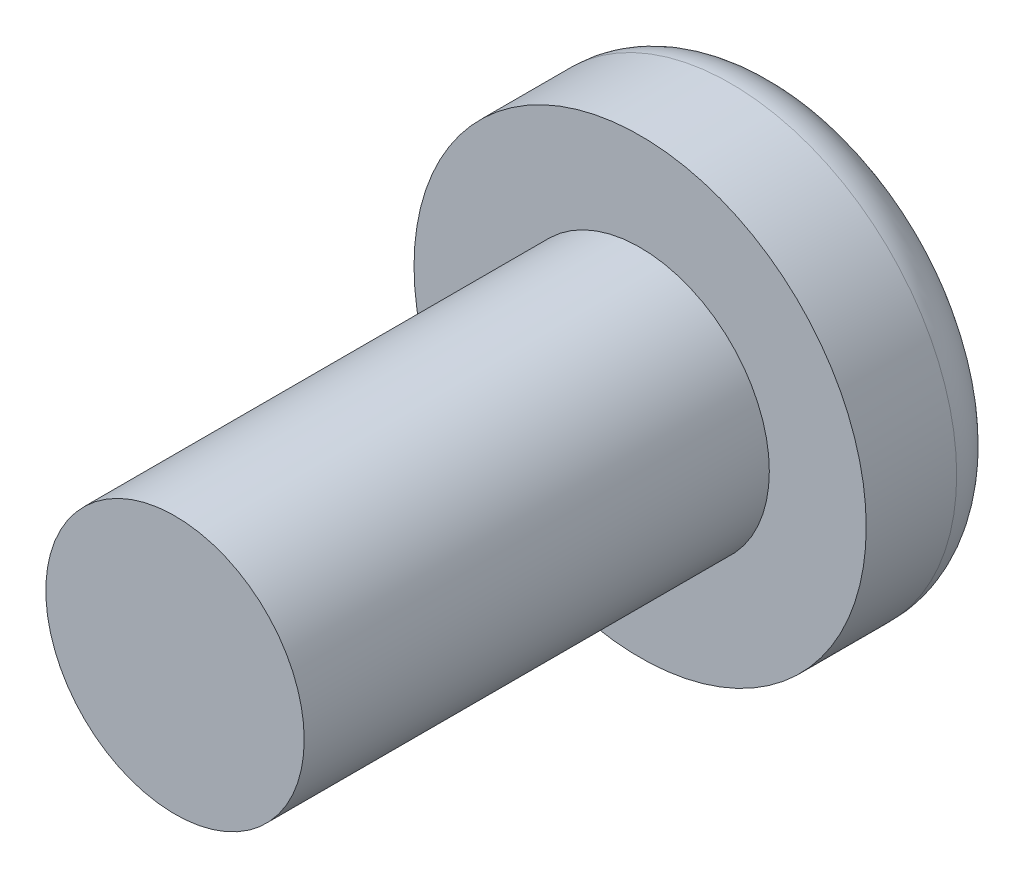
SolidWorks part; units mm, degrees
ref_plane "前视基准面" through (0, 0, 0) normal (0, 0, 1) x (1, 0, 0)
ref_plane "上视基准面" through (0, 0, 0) normal (0, 1, 0) x (1, 0, 0)
ref_plane "右视基准面" through (0, 0, 0) normal (1, 0, 0) x (0, 0, -1)
sketch "草图1" plane through (0, 0, 0) normal (0, 0, 1) x (1, 0, 0)
  circle A0 centre (0, 0) radius 5
  dimension "D1" = 10
extrude "凸台-拉伸1" add sketch "草图1" along normal blind 18
sketch "草图2" plane through (0, 0, 0) normal (0, 0, -1) x (-1, 0, 0)
  circle A0 centre (0, 0) radius 8.75
  dimension "D1" = 17.5
extrude "凸台-拉伸2" add sketch "草图2" along normal blind 5.5
fillet "圆角1" radius 2 1 edges at (-8.75, 0, -5.5)
sketch "草图3" plane through (0, 0, -5.5) normal (0, 0, -1) x (-1, 0, 0)
  line L0 (-0.7071, 0.7071) -> (-0.7071, 6.0064)
  line L1 (1, -1) -> (-1, -1) construction
  line L2 (1, -1) -> (1, 1) construction
  line L3 (1, 1) -> (-1, 1) construction
  line L4 (-1, -1) -> (-1, 1) construction
  line L5 (1, -1) -> (-1, 1) construction
  line L6 (1, 1) -> (-1, -1) construction
  line L7 (0.7071, 0.7071) -> (0.7071, 6.0064)
  line L8 (0.7071, 6.0064) -> (-0.7071, 6.0064)
  line L9 (0.7071, 0.7071) -> (6.0064, 0.7071)
  line L10 (0.7071, -0.7071) -> (6.0064, -0.7071)
  line L11 (6.0064, -0.7071) -> (6.0064, 0.7071)
  line L12 (0.7071, -0.7071) -> (0.7071, -6.0064)
  line L13 (-0.7071, -0.7071) -> (-0.7071, -6.0064)
  line L14 (-0.7071, -6.0064) -> (0.7071, -6.0064)
  line L15 (-0.7071, -0.7071) -> (-6.0064, -0.7071)
  line L16 (-0.7071, 0.7071) -> (-6.0064, 0.7071)
  line L17 (-6.0064, 0.7071) -> (-6.0064, -0.7071)
  circle A0 centre (0, 0) radius 1 construction
  dimension "D1" = 4
extrude "切除-拉伸1" cut sketch "草图3" against normal blind 2
